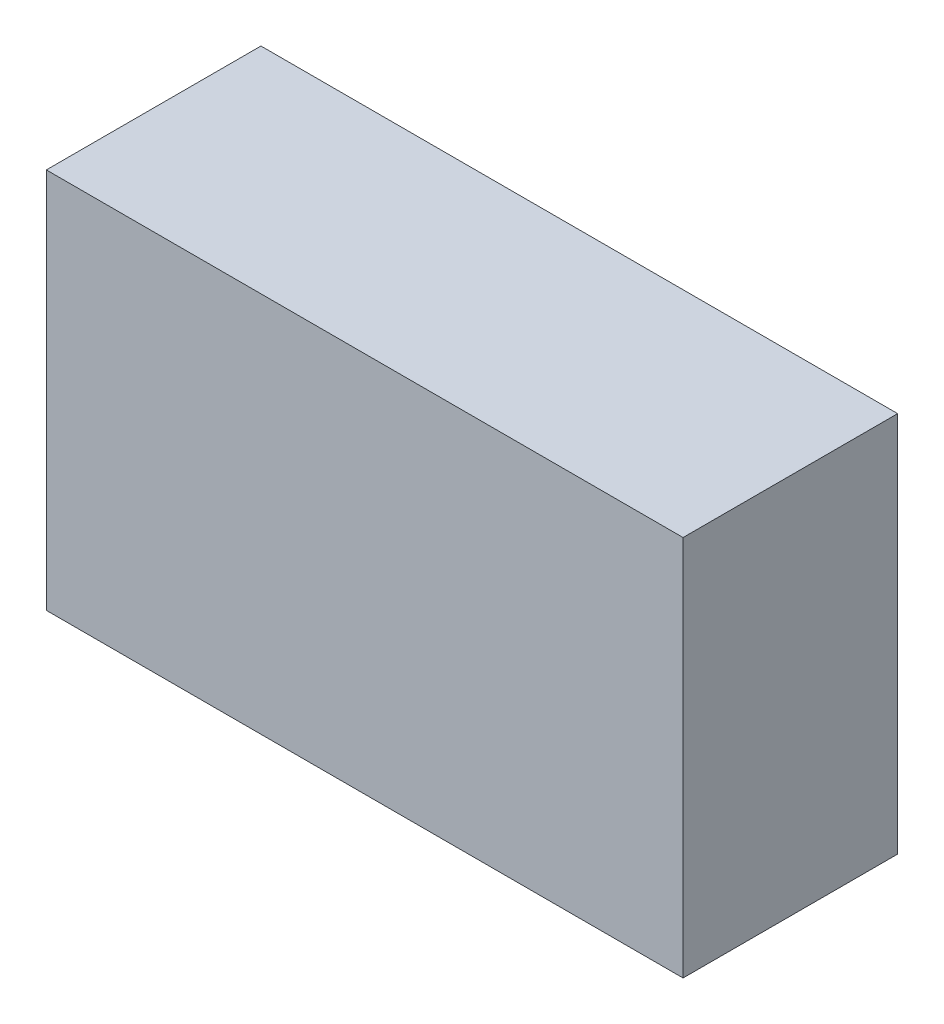
SolidWorks part; units mm, degrees
ref_plane "前基準面" through (0, 0, 0) normal (0, 0, 1) x (1, 0, 0)
ref_plane "上基準面" through (0, 0, 0) normal (0, 1, 0) x (1, 0, 0)
ref_plane "右基準面" through (0, 0, 0) normal (1, 0, 0) x (0, 0, -1)
sketch "草圖1" plane through (0, 0, 0) normal (0, 0, 1) x (1, 0, 0)
  line L1 (0, 0) -> (29.6709, 0)
  line L2 (0, 0) -> (0, 17.7758)
  line L3 (0, 17.7758) -> (29.6709, 17.7758)
  line L4 (29.6709, 0) -> (29.6709, 17.7758)
extrude "填料-伸長1" add sketch "草圖1" along normal blind 10
